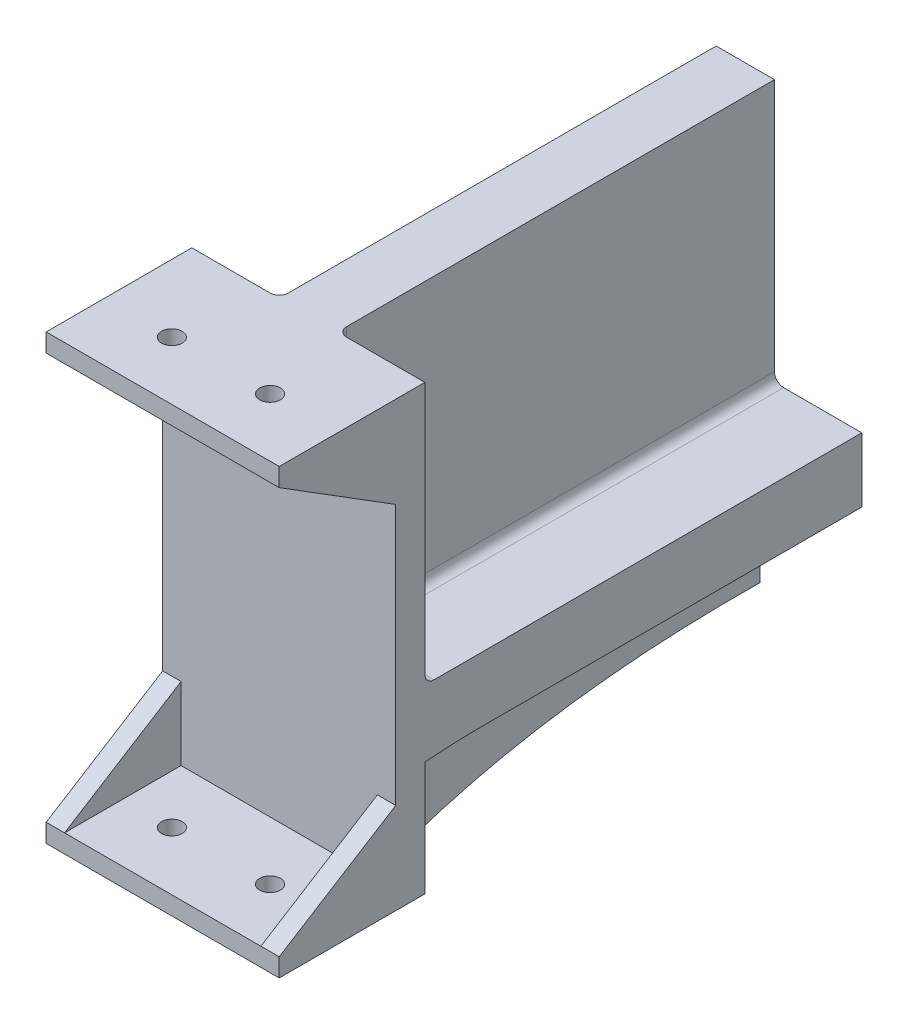
SolidWorks part; units mm, degrees
material "ABS"
ref_plane "X-Y Datum" through (0, 0, 0) normal (0, 0, 1) x (1, 0, 0)
ref_plane "X-Z Datum" through (0, 0, 0) normal (0, 1, 0) x (1, 0, 0)
ref_plane "Y-Z Datum" through (0, 0, 0) normal (1, 0, 0) x (0, 0, -1)
sketch "Sketch1" plane through (0, 0, 0) normal (0, 0, 1) x (1, 0, 0)
  line L1 (-25.4, 48.2854) -> (25.4, 48.2854)
  line L2 (-25.4, 48.2854) -> (-25.4, -48.2854)
  line L3 (-25.4, -48.2854) -> (25.4, -48.2854)
  line L4 (25.4, 48.2854) -> (25.4, -48.2854)
  line L5 (-25.4, 48.2854) -> (25.4, -48.2854) construction
  line L6 (-25.4, -48.2854) -> (25.4, 48.2854) construction
  point P0 (0, 0)
  dimension "D1" = 96.5708
  dimension "D2" = 50.8
extrude "Boss-Extrude1" add sketch "Sketch1" along normal blind 101.6
sketch "Sketch2" plane through (0, -48.2854, 0) normal (0, -1, 0) x (1, 0, 0)
  line L0 (-3.175, 0) -> (3.175, 0)
  line L1 (-25.4, 0) -> (25.4, 0) construction
  line L2 (0, 0) -> (0, 101.6) construction
  line L3 (-25.4, 101.6) -> (25.4, 101.6) construction
  line L4 (-25.4, 95.25) -> (-15.875, 95.25)
  line L5 (-25.4, 101.6) -> (-25.4, 0) construction
  line L6 (25.4, 95.25) -> (15.875, 95.25)
  arc A0 (-15.875, 95.25) -> (-3.175, 0) centre (-333.345, 4.449) cw
  arc A1 (15.875, 95.25) -> (3.175, 0) centre (333.345, 4.449) ccw
  point P5 (0, 0)
  point P15 (0, 0)
  point P20 (-15.0215, 97.0184)
  line M5 (-25.4, 0) -> (25.4, 0)
  line M6 (25.4, 0) -> (25.4, 101.6)
  line M8 (-25.4, 101.6) -> (-25.4, 0)
  dimension "D2" = 330.2
  dimension "D1" = 6.35
  dimension "D3" = 6.35
  dimension "D4" = 9.525
extrude "Cut-Extrude1" cut sketch "Sketch2" against normal blind 25.4 and the other way through all contours A0 M8 M5 | A1 M6 M5 region at (15.8837, -48.2854, 42.1228) region at (-15.8837, -48.2854, 42.1228)
fillet "Fillet1" radius 12.7 2 edges at (6.0416, -22.8854, 48.0895) (-6.0416, -22.8854, 48.0895)
fillet "Fillet2" radius 12.7 2 edges at (-15.875, -41.9354, 95.25) (15.875, -41.9354, 95.25)
sketch "Sketch4" plane through (0, 0, 101.6) normal (0, 0, 1) x (1, 0, 0)
  line L0 (25.4, -48.2854) -> (25.4, 48.2854) construction
  line L1 (-25.4, -48.2854) -> (25.4, -48.2854)
  line L2 (-25.4, -48.2854) -> (-25.4, -44.2854)
  line L3 (-25.4, -44.2854) -> (25.4, -44.2854)
  line L4 (25.4, -48.2854) -> (25.4, -44.2854)
  dimension "D1" = 4
extrude "Boss-Extrude2" add sketch "Sketch4" along normal blind 25.4
sketch "Sketch5" plane through (25.4, 0, 0) normal (1, 0, 0) x (0, 0, -1)
  line L0 (-127, -44.2854) -> (-101.6, -28.4104)
  line L1 (-127, -44.2854) -> (-101.6, -44.2854) construction
  line L2 (-101.6, -44.2854) -> (-101.6, 48.2854) construction
  point P5 (-101.6, -28.4104)
  line M7 (-101.6, 48.2854) -> (-101.6, -44.2854)
  line M8 (-101.6, -44.2854) -> (-127, -44.2854)
  dimension "D1" = 15.875
extrude "Boss-Extrude3" add sketch "Sketch5" against normal blind 4 contours L0 M8 M7 region at (25.4, -38.9937, 110.0667)
mirror "Mirror1" about plane through (0, 0, 0) normal (1, 0, 0) of "Boss-Extrude3"
sketch "Sketch6" plane through (0, -44.2854, 0) normal (0, 1, 0) x (1, 0, 0)
  line L0 (21.4, -114.3) -> (-21.4, -114.3) construction
  line L1 (21.4, -127) -> (21.4, -101.6) construction
  line L2 (-21.4, -101.6) -> (-21.4, -127) construction
  line L3 (21.4, -114.3) -> (0, -114.3) construction
  line L4 (0, -114.3) -> (10.7, -114.3) construction
  line L5 (10.7, -114.3) -> (10.7, -129.9826) construction
  line L6 (0, -133.4996) -> (0, -95.1004) construction
  circle A0 centre (10.7, -114.3) radius 2 construction
  circle A1 centre (-10.7, -114.3) radius 2 construction
  point P12 (0, -114.3)
  dimension "D1" = 4
hole_wizard "M4 Clearance Hole1" positions "Sketch7" profile "Sketch8" hole size "M4" standard "ANSI Metric" end condition through all
sketch "Sketch7" plane through (0, -44.2854, 0) normal (0, 1, 0) x (1, 0, 0)
  point P0 (-10.7, -114.3)
  point P3 (10.7, -114.3)
sketch "Sketch8" plane through (-10.7, -44.2854, 114.3) normal (1, 0, 0) x (0, 0, 1)
  line L0 (0, 0) -> (0, 4)
  line L1 (0, 4) -> (2.25, 4)
  line L2 (2.25, 4) -> (2.25, 0)
  line L5 (2.25, 0) -> (0, 0)
  line L11 (0, -6.35) -> (0, 107.95) construction
  dimension "Thru Hole Dia." = 4.5
  dimension "Thru Hole Depth" = 4
mirror "Mirror2" about plane through (0, 0, 0) normal (0, 1, 0) of "M4 Clearance Hole1", "Boss-Extrude3", "Mirror1", "Boss-Extrude2"
sketch "Sketch10" plane through (0, 0, 0) normal (0, 0, -1) x (-1, 0, 0)
  line L0 (-6.35, -8.8646) -> (-6.35, 48.2854)
  line L1 (-25.4, 48.2854) -> (25.4, 48.2854) construction
  line L2 (-6.35, -8.8646) -> (-25.4, -8.8646)
  line L3 (-25.4, -22.8854) -> (-25.4, 48.2854) construction
  line L4 (0, 53.1139) -> (0, -53.1139) construction
  line L5 (6.35, -8.8646) -> (25.4, -8.8646)
  line L6 (6.35, -8.8646) -> (6.35, 48.2854)
  point P13 (0, 0)
  line M10 (25.4, -22.8854) -> (25.4, 48.2854)
  line M11 (25.4, 48.2854) -> (-25.4, 48.2854)
  line M12 (-25.4, 48.2854) -> (-25.4, -22.8854)
  dimension "D1" = 19.05
  dimension "D2" = 57.15
extrude "Cut-Extrude2" cut sketch "Sketch10" against normal blind 95.25 contours L2 L0 M11 M12 | L6 L5 M10 M11 region at (15.875, 19.7104, 0) region at (-15.875, 19.7104, 0)
fillet "Fillet3" radius 2 6 edges at (-15.875, -8.8646, 95.25) (15.875, -8.8646, 95.25) (-6.35, -8.8646, 47.625) (-6.35, 19.7104, 95.25) (6.35, 19.7104, 95.25) (6.35, -8.8646, 47.625)
